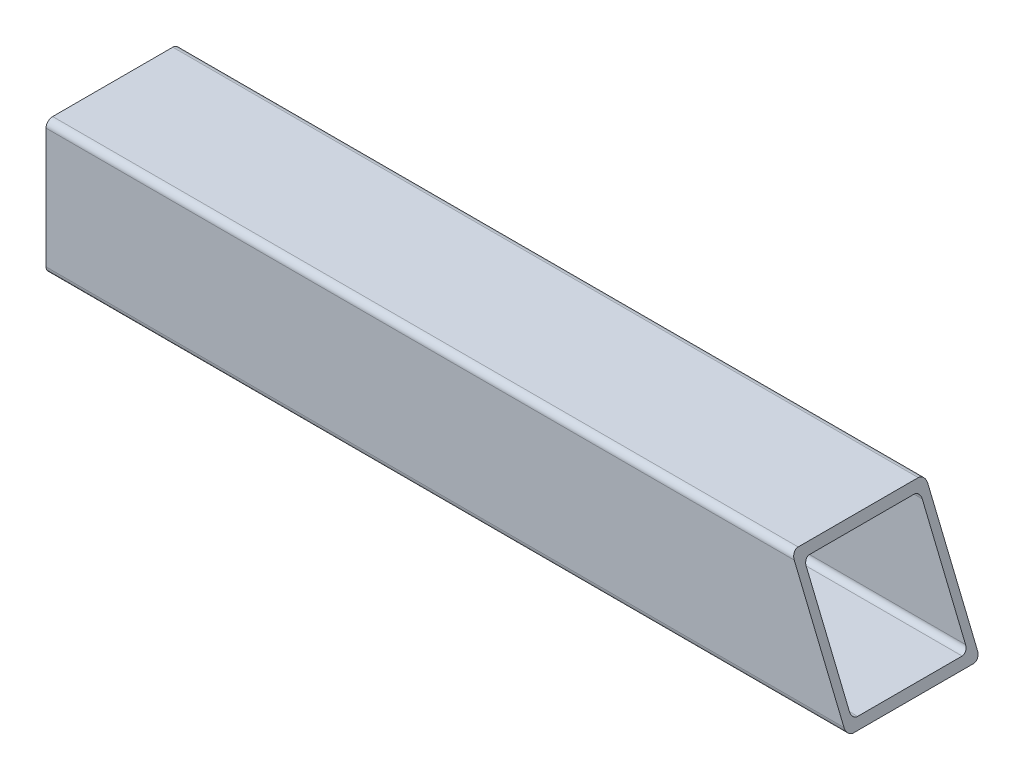
SolidWorks part; units mm, degrees
ref_plane "Front" through (0, 0, 0) normal (0, 0, 1) x (1, 0, 0)
ref_plane "Top" through (0, 0, 0) normal (0, 1, 0) x (1, 0, 0)
ref_plane "Right" through (0, 0, 0) normal (1, 0, 0) x (0, 0, -1)
sketch "Sketch1" plane through (0, 0, 0) normal (1, 0, 0) x (0, 0, -1)
  line L0 (-11.049, 0) -> (-12.7, 0) construction
  line L1 (11.43, -12.7) -> (-11.43, -12.7) construction
  line L2 (12.7, -11.43) -> (12.7, 11.43) construction
  line L3 (11.43, 12.7) -> (-11.43, 12.7) construction
  line L4 (-12.7, -11.43) -> (-12.7, 11.43) construction
  line L5 (12.7, -12.7) -> (-12.7, 12.7) construction
  line L6 (12.7, 12.7) -> (-12.7, -12.7) construction
  line L7 (9.9441, 11.049) -> (-9.9441, 11.049) construction
  line L8 (11.049, 9.9441) -> (11.049, -9.9441) construction
  line L9 (9.9441, -11.049) -> (-9.9441, -11.049) construction
  line L10 (-11.049, 9.9441) -> (-11.049, -9.9441) construction
  line L11 (11.049, 11.049) -> (-11.049, -11.049) construction
  line L12 (11.049, -11.049) -> (-11.049, 11.049) construction
  line L13 (0, -11.049) -> (0, -12.7) construction
  line L14 (11.049, -9.9441) -> (11.049, -12.7) construction
  line L15 (11.049, 0) -> (12.7, 0) construction
  line L16 (11.049, -12.7) -> (12.7, -12.7) construction
  arc A0 (-9.9441, -11.049) -> (-11.049, -9.9441) centre (-9.9441, -9.9441) cw construction
  arc A1 (11.049, -9.9441) -> (9.9441, -11.049) centre (9.9441, -9.9441) cw construction
  arc A2 (9.9441, 11.049) -> (11.049, 9.9441) centre (9.9441, 9.9441) cw construction
  arc A3 (-9.9441, 11.049) -> (-11.049, 9.9441) centre (-9.9441, 9.9441) ccw construction
  arc A4 (11.43, -12.7) -> (12.7, -11.43) centre (11.43, -11.43) ccw construction
  arc A5 (12.7, 11.43) -> (11.43, 12.7) centre (11.43, 11.43) ccw construction
  arc A6 (-11.43, 12.7) -> (-12.7, 11.43) centre (-11.43, 11.43) ccw construction
  arc A7 (-11.43, -12.7) -> (-12.7, -11.43) centre (-11.43, -11.43) cw construction
  point P0 (0, 0)
  point P6 (0, 0)
  dimension "D2" = 1.1049
  dimension "D3" = 1.27
  dimension "Outside Width" = 25.4
  dimension "Ouside Height" = 25.4
  dimension "Inside Height" = 22.098
  dimension "Wall Thickness" = 1.651
sketch "Sketch2" plane through (0, 0, 0) normal (0, 0, 1) x (1, 0, 0)
  line L0 (-76.2, 0) -> (76.2, 0) construction
  point P3 (-52.451, 0)
  point P4 (52.451, 0)
  dimension "Length" = 152.4
  dimension "D1" = 23.749
  dimension "D2" = 23.749
sketch "Sketch4" plane through (0, 0, 0) normal (1, 0, 0) x (0, 0, -1)
  line L8 (12.7, -11.43) -> (12.7, 11.43)
  line L9 (11.43, 12.7) -> (-11.43, 12.7)
  line L10 (-12.7, -11.43) -> (-12.7, 11.43)
  line L11 (11.43, -12.7) -> (-11.43, -12.7)
  line L12 (11.049, 9.9441) -> (11.049, -9.9441)
  line L13 (9.9441, -11.049) -> (-9.9441, -11.049)
  line L14 (-11.049, 9.9441) -> (-11.049, -9.9441)
  line L15 (9.9441, 11.049) -> (-9.9441, 11.049)
  arc A8 (12.7, 11.43) -> (11.43, 12.7) centre (11.43, 11.43) ccw
  arc A9 (-11.43, 12.7) -> (-12.7, 11.43) centre (-11.43, 11.43) ccw
  arc A10 (-12.7, -11.43) -> (-11.43, -12.7) centre (-11.43, -11.43) ccw
  arc A11 (11.43, -12.7) -> (12.7, -11.43) centre (11.43, -11.43) ccw
  arc A12 (9.9441, -11.049) -> (11.049, -9.9441) centre (9.9441, -9.9441) ccw
  arc A13 (-11.049, -9.9441) -> (-9.9441, -11.049) centre (-9.9441, -9.9441) ccw
  arc A14 (-9.9441, 11.049) -> (-11.049, 9.9441) centre (-9.9441, 9.9441) ccw
  arc A15 (11.049, 9.9441) -> (9.9441, 11.049) centre (9.9441, 9.9441) ccw
extrude "Boss-Extrude1" add sketch "Sketch4" along normal up to vertex (-76.2 mm away) and the other way up to vertex (-76.2 mm away) up to point (-76.2, 0, 0) other way up to point (76.2, 0, 0)
sketch "Sketch5" plane through (0, 0, 12.7) normal (0, 0, 1) x (1, 0, 0)
  line L0 (76.2, -12.7) -> (65.679, 12.7)
  line L1 (76.2, 12.7) -> (-76.2, 12.7) construction
  line L2 (65.679, 12.7) -> (76.2, 12.7)
  line L3 (76.2, 12.7) -> (76.2, -12.7)
  dimension "D1" = 22.5
extrude "Cut-Extrude1" cut sketch "Sketch5" against normal through all
equation "\"D3@Sketch1\"=\"Outside Width@Sketch1\"*.05"
equation "\"D2@Sketch1\" = \"Inside Height@Sketch1\" * .05"
equation "\"D1@Sketch2\"=\"Outside Width@Sketch1\"-\"Wall Thickness@Sketch1\""
equation "\"D2@Sketch2\"=\"D1@Sketch2\""
